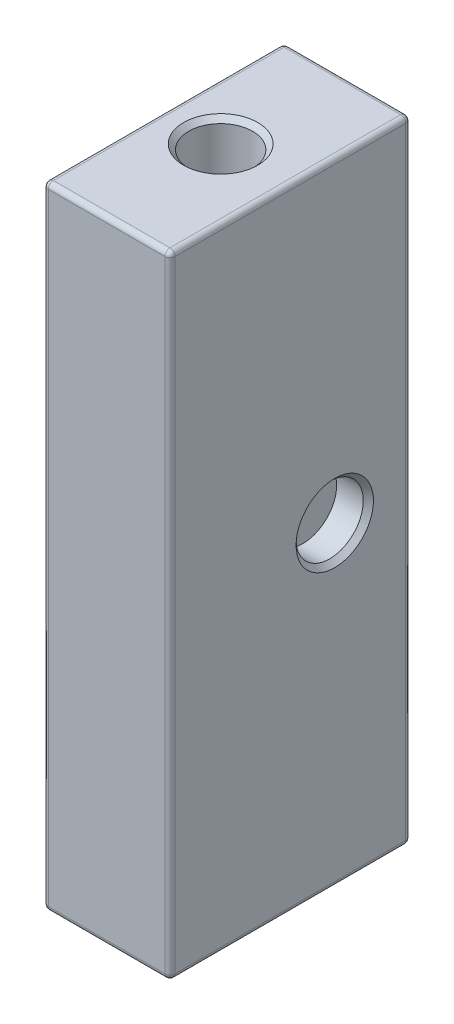
SolidWorks part; units mm, degrees
material "ABS"
ref_plane "Front Plane" through (0, 0, 0) normal (0, 0, 1) x (1, 0, 0)
ref_plane "Top Plane" through (0, 0, 0) normal (0, 1, 0) x (1, 0, 0)
ref_plane "Right Plane" through (0, 0, 0) normal (1, 0, 0) x (0, 0, -1)
sketch "Sketch1" plane through (0, 0, 0) normal (0, 1, 0) x (1, 0, 0)
  line L6 (5, -9.5) -> (-5, -9.5)
  line L9 (5, -9.5) -> (5, 9.5)
  line L10 (5, 9.5) -> (-5, 9.5)
  line L11 (-5, -9.5) -> (-5, 9.5)
  line L13 (5, -9.5) -> (-5, 9.5) construction
  line L14 (5, 9.5) -> (-5, -9.5) construction
  circle A3 centre (-0.5, 0) radius 2.525 construction
  circle A4 centre (-0.5, 0) radius 2.525
  point P0 (0, 0)
  dimension "D1" = 10
  dimension "D3" = 19
extrude "Boss-Extrude1" add sketch "Sketch1" along normal mid plane 49.8
sketch "Sketch2" plane through (5, 0, 0) normal (1, 0, 0) x (0, 0, -1)
  line L3 (-9.5, 25) -> (-9.5, -25) construction
  circle A0 centre (3.5, 0) radius 2.65
  dimension "D1" = 5.3
  dimension "D2" = 13
extrude "Cut-Extrude1" cut sketch "Sketch2" against normal blind 2.5
fillet "Fillet1" radius 0.4 12 edges at (5, 0, -9.5) (0, 24.9, -9.5) (0, -24.9, -9.5) (0, 24.9, 9.5) (5, 0, 9.5) (0, -24.9, 9.5) (-5, 0, -9.5) (-5, 24.9, 0) (-5, 0, 9.5) (-5, -24.9, 0) (5, 24.9, 0) (5, -24.9, 0)
chamfer "Chamfer1" distance 0.4 angle 45 2 edges at (5, 0, -6.15) (-0.5, 24.9, 2.525)
